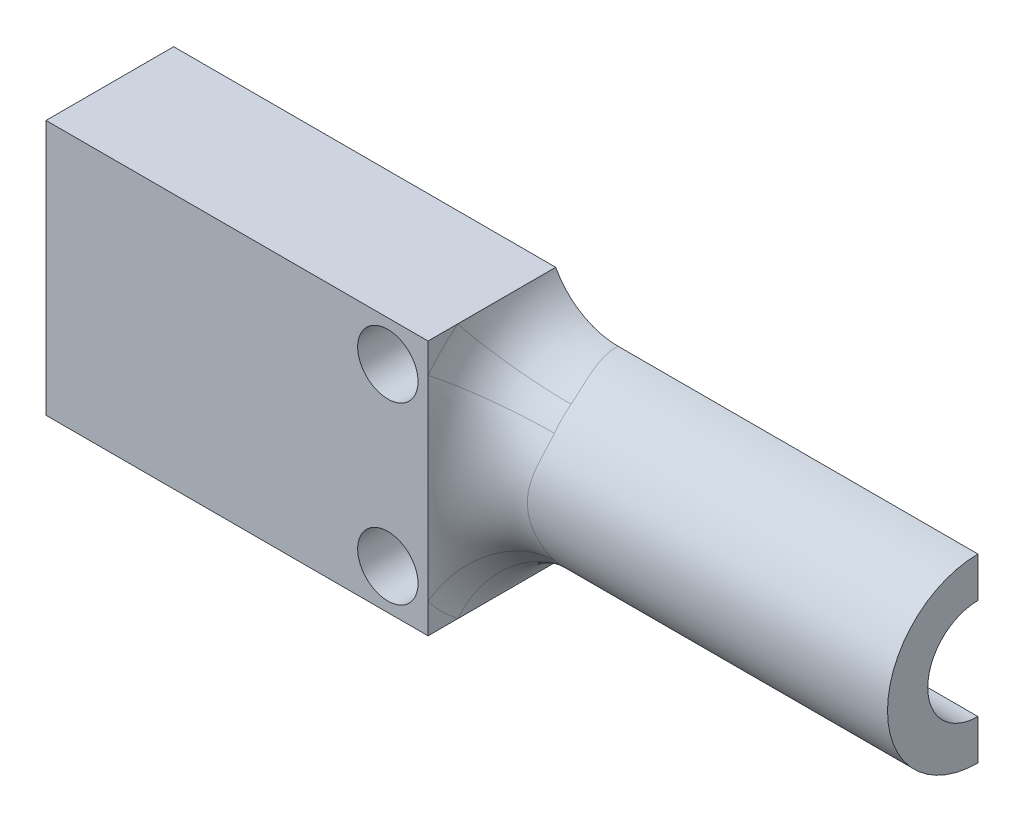
SolidWorks part; units mm, degrees
material "PLA"
ref_plane "Ebene vorne" through (0, 0, 0) normal (1, 0, 0) x (0, 1, 0)
ref_plane "Ebene oben" through (0, 0, 0) normal (0, 0, 1) x (0, 1, 0)
ref_plane "Ebene rechts" through (0, 0, 0) normal (0, 1, 0) x (-1, 0, 0)
sketch "Skizze5" plane through (0, 0, 0) normal (1, 0, 0) x (0, 1, 0)
  line L1 (-12.7, -12.7) -> (12.7, -12.7)
  line L2 (-12.7, -12.7) -> (-12.7, 12.7)
  line L3 (-12.7, 12.7) -> (12.7, 12.7)
  line L4 (12.7, -12.7) -> (12.7, 12.7)
  line L5 (-12.7, -12.7) -> (12.7, 12.7) construction
  line L6 (-12.7, 12.7) -> (12.7, -12.7) construction
  point P0 (0, 0)
  dimension "D1" = 25.4
  dimension "D2" = 25.4
extrude "Motorarm" add sketch "Skizze5" along normal blind 60 and the other way blind 20
sketch "Skizze6" plane through (60, 0, 0) normal (1, 0, 0) x (0, 1, 0)
  circle A0 centre (0, 0) radius 5
  dimension "D1" = 10
extrude "Welle" cut sketch "Skizze6" against normal blind 100
sketch "Skizze7" plane through (-20, 0, 0) normal (-1, 0, 0) x (0, -1, 0)
  line L5 (-8.5, -8.5) -> (8.5, 8.5) construction
  line L6 (-8.5, 8.5) -> (8.5, -8.5) construction
  circle A0 centre (-8.5, 8.5) radius 2
  circle A1 centre (8.5, 8.5) radius 2
  circle A2 centre (-8.5, -8.5) radius 2
  circle A3 centre (8.5, -8.5) radius 2
  point P0 (0, 0)
  dimension "D1" = 17
  dimension "D2" = 17
extrude "Löcher AS5600" cut sketch "Skizze7" against normal blind 7
sketch "Skizze9" plane through (0, 0, -12.7) normal (0, 0, -1) x (1, 0, 0)
  line L8 (0, 9.5) -> (-8.2272, 4.75) construction
  line L9 (-8.2272, 4.75) -> (-8.2272, -4.75) construction
  line L10 (-8.2272, -4.75) -> (0, -9.5) construction
  line L11 (0, -9.5) -> (8.2272, -4.75) construction
  line L12 (8.2272, -4.75) -> (8.2272, 4.75) construction
  line L13 (8.2272, 4.75) -> (0, 9.5) construction
  circle A4 centre (0, 0) radius 8.2272 construction
  circle A5 centre (0, 9.5) radius 2
  circle A6 centre (8.2272, 4.75) radius 2
  circle A7 centre (8.2272, -4.75) radius 2
  circle A8 centre (0, -9.5) radius 2
  circle A9 centre (-8.2272, -4.75) radius 2
  circle A10 centre (-8.2272, 4.75) radius 2
  circle A11 centre (0, 0) radius 12.7 construction
extrude "Löcher Motoraufnahme" cut sketch "Skizze9" against normal blind 7
sketch "Skizze10" plane through (0, 0, 0) normal (1, 0, 0) x (0, 1, 0)
  circle A0 centre (0, 0) radius 6.5
  dimension "D1" = 13
extrude "Kugellager 1" cut sketch "Skizze10" along normal blind 5 from offset 12
sketch "Skizze11" plane through (0, 0, 0) normal (1, 0, 0) x (0, 1, 0)
  circle A0 centre (0, 0) radius 6.5
  dimension "D1" = 13
extrude "Kugellager 2" cut sketch "Skizze11" along normal blind 5 from offset 40
sketch "Skizze12" plane through (0, 0, 0) normal (1, 0, 0) x (0, 1, 0)
  circle A1 centre (0, 0) radius 9
  dimension "D1" = 18
extrude "Materialreduzierung" cut sketch "Skizze12" along normal blind 42 from offset 18 flip side to cut
fillet "Übergang" radius 7 1 edges at (18, 0, -9)
sketch "Skizze14" plane through (0, 0, -12.7) normal (0, 0, -1) x (1, 0, 0)
  line L15 (18, 12.7) -> (14, 12.7) construction
  line L16 (18, 12.7) -> (18, 8.7) construction
  line L17 (18, 8.7) -> (14, 8.7) construction
  line L18 (14, 12.7) -> (14, 8.7) construction
  line L19 (17.3, 8.7) -> (15.65, 11.5579)
  line L20 (15.65, 11.5579) -> (12.35, 11.5579)
  line L21 (12.35, 11.5579) -> (10.7, 8.7)
  line L22 (10.7, 8.7) -> (12.35, 5.8421)
  line L23 (12.35, 5.8421) -> (15.65, 5.8421)
  line L24 (15.65, 5.8421) -> (17.3, 8.7)
  line L25 (18, -12.7) -> (14, -12.7) construction
  line L26 (18, -12.7) -> (18, -8.7) construction
  line L27 (18, -8.7) -> (14, -8.7) construction
  line L28 (14, -12.7) -> (14, -8.7) construction
  line L29 (17.3, -8.7) -> (15.65, -5.8421)
  line L30 (15.65, -5.8421) -> (12.35, -5.8421)
  line L31 (12.35, -5.8421) -> (10.7, -8.7)
  line L32 (10.7, -8.7) -> (12.35, -11.5579)
  line L33 (12.35, -11.5579) -> (15.65, -11.5579)
  line L34 (15.65, -11.5579) -> (17.3, -8.7)
  circle A0 centre (14, 8.7) radius 3.3 construction
  circle A1 centre (14, 8.7) radius 2.8579 construction
  circle A2 centre (14, -8.7) radius 3.3 construction
  circle A3 centre (14, -8.7) radius 2.8579 construction
  dimension "D3" = 4
  dimension "D1" = 4
  dimension "D2" = 4
  dimension "D4" = 4
extrude "Platz für Muttern" cut sketch "Skizze14" against normal blind 3
sketch "Skizze17" plane through (0, 0, -12.7) normal (0, 0, -1) x (1, 0, 0)
  circle A0 centre (14, -8.7) radius 3.3 construction
  circle A1 centre (14, -8.7) radius 1.6
  circle A2 centre (14, 8.7) radius 3.3 construction
  circle A3 centre (14, 8.7) radius 1.6
  dimension "D1" = 3.2
extrude "Platz für Stange" cut sketch "Skizze17" against normal blind 25.4
sketch "Skizze18" plane through (0, 0, 12.7) normal (0, 0, 1) x (1, 0, 0)
  circle A0 centre (14, 8.7) radius 3
  circle A1 centre (14, -8.7) radius 3
  dimension "D1" = 6
extrude "Platz für Schraubenkopf" cut sketch "Skizze18" against normal blind 6
sketch "Skizze21" plane through (0, 0, 0) normal (0, 0, 1) x (0, 1, 0)
  line L0 (-9, -60) -> (9, -60) construction
  line L1 (-12.7, 20) -> (-8.7, 20) construction
  line L2 (-12.7, 20) -> (-12.7, 10) construction
  line L3 (-12.7, 10) -> (-8.7, 10) construction
  line L4 (-8.7, 20) -> (-8.7, 10) construction
  line L5 (12.7, 20) -> (8.7, 20) construction
  line L6 (12.7, 20) -> (12.7, 10) construction
  line L7 (12.7, 10) -> (8.7, 10) construction
  line L8 (8.7, 20) -> (8.7, 10) construction
  line L9 (9, -60) -> (7, -60) construction
  line L10 (9, -60) -> (9, -54) construction
  line L11 (9, -54) -> (7, -54) construction
  line L12 (7, -60) -> (7, -54) construction
  line L14 (-9, -60) -> (-7, -60) construction
  line L15 (-9, -60) -> (-9, -54) construction
  line L16 (-9, -54) -> (-7, -54) construction
  line L17 (-7, -60) -> (-7, -54) construction
  circle A0 centre (-8.7, 10) radius 1
  circle A1 centre (8.7, 10) radius 1
  circle A2 centre (-7, -54) radius 1
  circle A3 centre (7, -54) radius 1
  dimension "D1" = 6
  dimension "D2" = 2
  dimension "D3" = 6
  dimension "D4" = 2
  dimension "D5" = 10
  dimension "D6" = 4
  dimension "D7" = 4
  dimension "D8" = 10
extrude "Platz für Fixierung" cut sketch "Skizze21" against normal blind 2.5 and the other way blind 2.5
split "Abspalten1" trim tools "Ebene oben" bodies to split 115 resulting bodies 116 117
delete or keep bodies "Körper-Löschen/beibehalten 2" type delete bodies bodies 117
